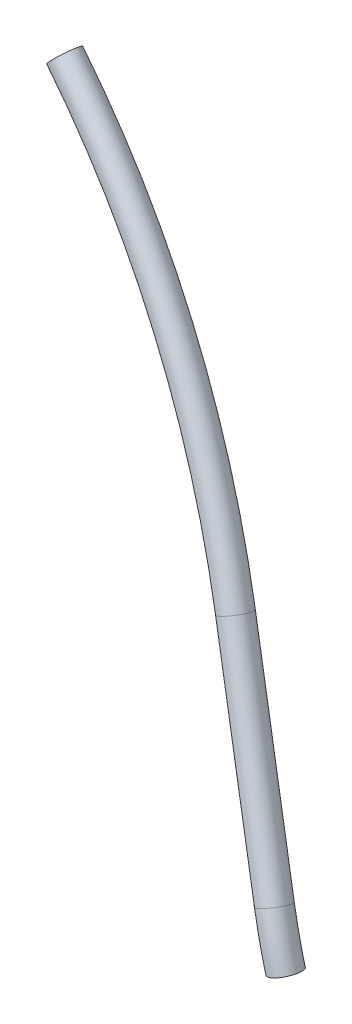
SolidWorks part; units mm, degrees
ref_plane "Front" through (0, 0, 0) normal (0, 0, 1) x (1, 0, 0)
ref_plane "Top" through (0, 0, 0) normal (0, 1, 0) x (1, 0, 0)
ref_plane "Right" through (0, 0, 0) normal (1, 0, 0) x (0, 0, -1)
ref_plane "Plane1" through (-67.8991, 165.7905, -18.373) normal (-0.377, 0.9206, -0.102) x (-0.9262, -0.3747, 0.0415)
sketch "Sketch1" plane through (-67.8991, 165.7905, -18.373) normal (-0.377, 0.9206, -0.102) x (-0.9262, -0.3747, 0.0415)
  point P0 (-7165.169, -16254.147)
ref_plane "Plane2" through (10442.5826, 3818.7785, -4132.4052) normal (-0.8803, -0.3219, 0.3484) x (0.3272, 0.1196, 0.9374)
ref_plane "Plane3" through (-2318.1676, -4447.1471, -13003.2975) normal (-0.1663, -0.3191, -0.933) x (-0.9861, 0.0538, 0.1574)
ref_axis "Axis1" through (6623.4709, 943.0069, -16440.8121) along (-0.4127, 0.8819, -0.228)
sketch "Sketch3" plane through (10442.5826, 3818.7785, -4132.4052) normal (-0.8803, -0.3219, 0.3484) x (0.3272, 0.1196, 0.9374)
  line L0 (-12875.9504, -2455.0592) -> (-12920.4495, -2048.6252) construction
  line L1 (-13130.9843, -1389.1751) -> (-13420.6602, -234.1203) construction
  arc A0 (-12875.9504, -2455.0592) -> (-12906.7291, -2283.3713) centre (-14145.6111, -2594.0702) ccw
sketch "Sketch4" plane through (-2318.1676, -4447.1471, -13003.2975) normal (-0.1663, -0.3191, -0.933) x (-0.9861, 0.0538, 0.1574)
  line L0 (-8268.3491, 7248.2582) -> (-8550.3512, 6991.2013) construction
  line L1 (-9067.9566, 6212.5139) -> (-8569.5345, 7294.0125) construction
  line L2 (-9138.8198, 6058.7517) -> (-9453.8145, 5375.262)
  arc A0 (-8268.3491, 7248.2582) -> (-9138.8198, 6058.7517) centre (-5767.9932, 4505.2645) ccw
  ellipse E1 centre (-9365.7938, 5334.6965) end of major axis (-9900.3884, 4174.7091) minor radius 96.9185 (-9453.8145, 5375.262) -> (-9525.8293, 5216.842) ccw construction
  point P8 (-9019.5776, 6294.9554)
  point P17 (-8763.2321, 6697.1446)
  dimension "D2" = 1483.8517
  dimension "D3" = 1219.2
  dimension "D4" = 741.934
  dimension "D1" = 752.5822
sketch "Sketch5" plane through (391.7606, -956.5691, 106.0077) normal (-0.377, 0.9206, -0.102) x (-0.9262, -0.3747, 0.0415)
  circle A0 centre (-7213.5442, -16106.2047) radius 50.8
  circle A1 centre (-7213.5442, -16106.2047) radius 50.8 construction
sweep "Sweep1" add profiles "Sketch5" path "Sketch3"
sketch "Sketch6" plane through (-381.71, 815.5946, -210.8851) normal (-0.4127, 0.8819, -0.228) x (-0.9109, -0.3996, 0.1033)
  circle A0 centre (-8108.4802, -15681.2625) radius 50.8
  circle A1 centre (-8108.4802, -15681.2625) radius 50.8 construction
sweep "Sweep2" add profiles "Sketch6" path "Sketch4"
